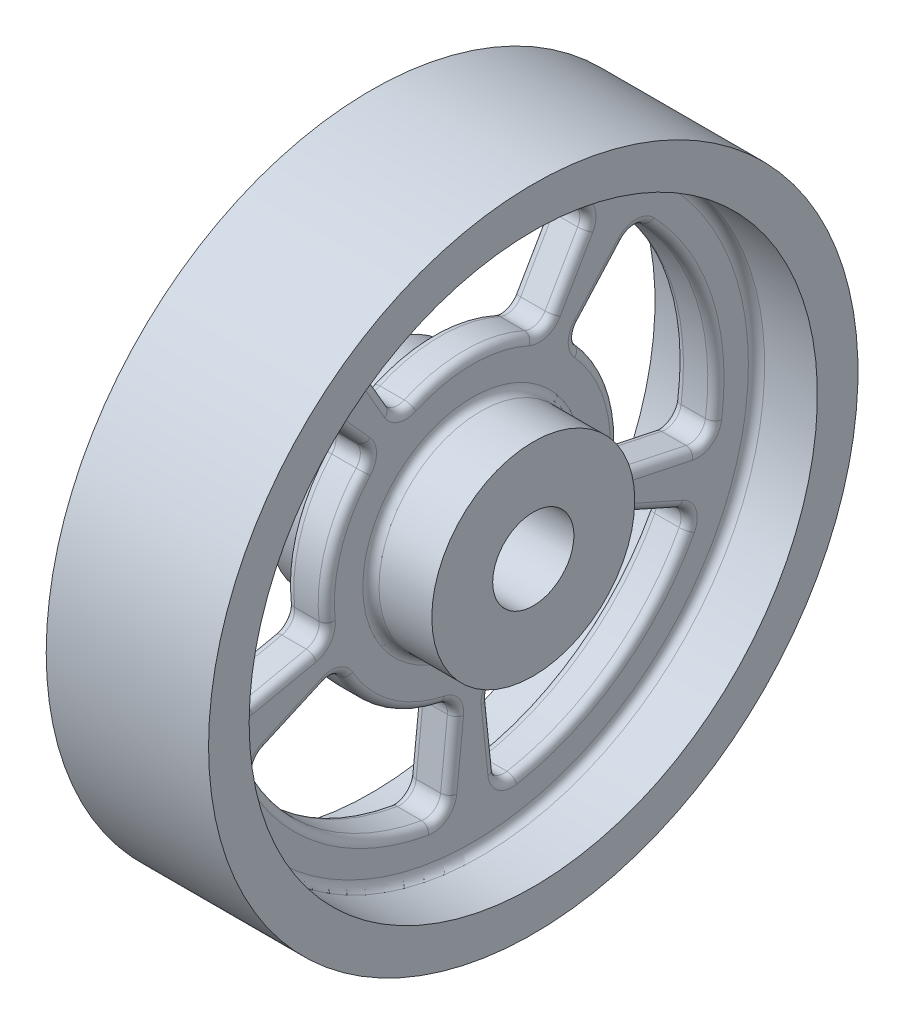
SolidWorks part; units mm, degrees
ref_plane "Front Plane" through (0, 0, 0) normal (0, 0, 1) x (1, 0, 0)
ref_plane "Top Plane" through (0, 0, 0) normal (0, 1, 0) x (1, 0, 0)
ref_plane "Right Plane" through (0, 0, 0) normal (1, 0, 0) x (0, 0, -1)
sketch "Sketch1" plane through (0, 0, 0) normal (0, 1, 0) x (1, 0, 0)
  line L0 (0, 0) -> (25.6742, 0) construction
  line L1 (0, 0) -> (0, 10.3933) construction
  line L2 (2.5, 35) -> (10, 35)
  line L3 (-10, 12.5) -> (-2.5, 12.5)
  line L4 (-10, 12.5) -> (-10, 5)
  line L5 (-10, 5) -> (10, 5)
  line L6 (10, 12.5) -> (10, 5)
  line L8 (-2.5, 12.5) -> (-2.5, 35)
  line L10 (2.5, 12.5) -> (2.5, 35)
  line L11 (-10, 40) -> (10, 40)
  line L12 (-10, 40) -> (-10, 35)
  line L13 (-10, 35) -> (-2.5, 35)
  line L14 (10, 40) -> (10, 35)
  line L15 (2.5, 12.5) -> (10, 12.5)
  dimension "D1" = 10
  dimension "D2" = 80
  dimension "D3" = 5
  dimension "D4" = 25
  dimension "D5" = 20
  dimension "D6" = 5
revolve "Revolve1" add sketch "Sketch1" angle 360 about L0
sketch "Sketch2" plane through (2.5, 0, 0) normal (1, 0, 0) x (0, 0, -1)
  line L0 (-9, 15.5885) -> (-15, 25.9808)
  line L2 (9, 15.5885) -> (15, 25.9808)
  line L3 (0, 18) -> (0, 34.3288) construction
  arc A0 (9, 15.5885) -> (-9, 15.5885) centre (0, 0) ccw
  arc A1 (15, 25.9808) -> (-15, 25.9808) centre (0, 0) ccw
  dimension "D1" = 60
  dimension "D2" = 30
  dimension "D3" = 18
extrude "Cut-Extrude1" cut sketch "Sketch2" against normal through all
fillet "Fillet1" radius 2 4 edges at (0, 25.9808, -15) (0, 15.5885, -9) (0, 25.9808, 15) (0, 15.5885, 9)
pattern_circular "CirPattern1" count 5 over 360 about axis through (0, 0, 0) along (-1, 0, 0) of "Cut-Extrude1", "Fillet1"
fillet "Fillet2" radius 1 84 edges at (-2.5, 0, 35) (-2.5, 0, 12.5) (-2.5, 25.7731, -14.1443) (-2.5, 20.7102, -11.9571) (-2.5, 16.3302, -8.8315) (-2.5, 18, 0) (-2.5, 16.3302, 8.8315) (-2.5, 20.7102, 11.9571) (-2.5, 25.7731, 14.1443) (-2.5, 30, 0) (-2.5, -5.4877, -28.8825) (-2.5, -4.972, -23.3915) (-2.5, -3.353, -18.26) (-2.5, 5.5623, -17.119) (-2.5, 13.4456, -12.8018) (-2.5, 17.7717, -16.0017) (-2.5, 21.4164, -20.1409) (-2.5, 9.2705, -28.5317) (-2.5, -29.1647, -3.7061) (-2.5, -23.7831, -2.4997) (-2.5, -18.4024, -2.4538) (-2.5, -14.5623, -10.5801) (-2.5, -8.0203, -16.7435) (-2.5, -9.7267, -21.8466) (-2.5, -12.5371, -26.592) (-2.5, -24.2705, -17.6336) (-2.5, -12.5371, 26.592) (-2.5, -9.7267, 21.8466) (-2.5, -8.0203, 16.7435) (-2.5, -14.5623, 10.5801) (-2.5, -18.4024, 2.4538) (-2.5, -23.7831, 2.4997) (-2.5, -29.1647, 3.7061) (-2.5, -24.2705, 17.6336) (-2.5, 21.4164, 20.1409) (-2.5, 17.7717, 16.0017) (-2.5, 13.4456, 12.8018) (-2.5, 5.5623, 17.119) (-2.5, -3.353, 18.26) (-2.5, -4.972, 23.3915) (-2.5, -5.4877, 28.8825) (-2.5, 9.2705, 28.5317) (2.5, 0, 12.5) (2.5, 0, 35) (2.5, 25.7731, -14.1443) (2.5, 30, 0) (2.5, 25.7731, 14.1443) (2.5, 20.7102, 11.9571) (2.5, 16.3302, 8.8315) (2.5, 18, 0) (2.5, 16.3302, -8.8315) (2.5, 20.7102, -11.9571) (2.5, -5.4877, -28.8825) (2.5, 9.2705, -28.5317) (2.5, 21.4164, -20.1409) (2.5, 17.7717, -16.0017) (2.5, 13.4456, -12.8018) (2.5, 5.5623, -17.119) (2.5, -3.353, -18.26) (2.5, -4.972, -23.3915) (2.5, -29.1647, -3.7061) (2.5, -24.2705, -17.6336) (2.5, -12.5371, -26.592) (2.5, -9.7267, -21.8466) (2.5, -8.0203, -16.7435) (2.5, -14.5623, -10.5801) (2.5, -18.4024, -2.4538) (2.5, -23.7831, -2.4997) (2.5, -12.5371, 26.592) (2.5, -24.2705, 17.6336) (2.5, -29.1647, 3.7061) (2.5, -23.7831, 2.4997) (2.5, -18.4024, 2.4538) (2.5, -14.5623, 10.5801) (2.5, -8.0203, 16.7435) (2.5, -9.7267, 21.8466) (2.5, 21.4164, 20.1409) (2.5, 9.2705, 28.5317) (2.5, -5.4877, 28.8825) (2.5, -4.972, 23.3915) (2.5, -3.353, 18.26) (2.5, 5.5623, 17.119) (2.5, 13.4456, 12.8018) (2.5, 17.7717, 16.0017)
